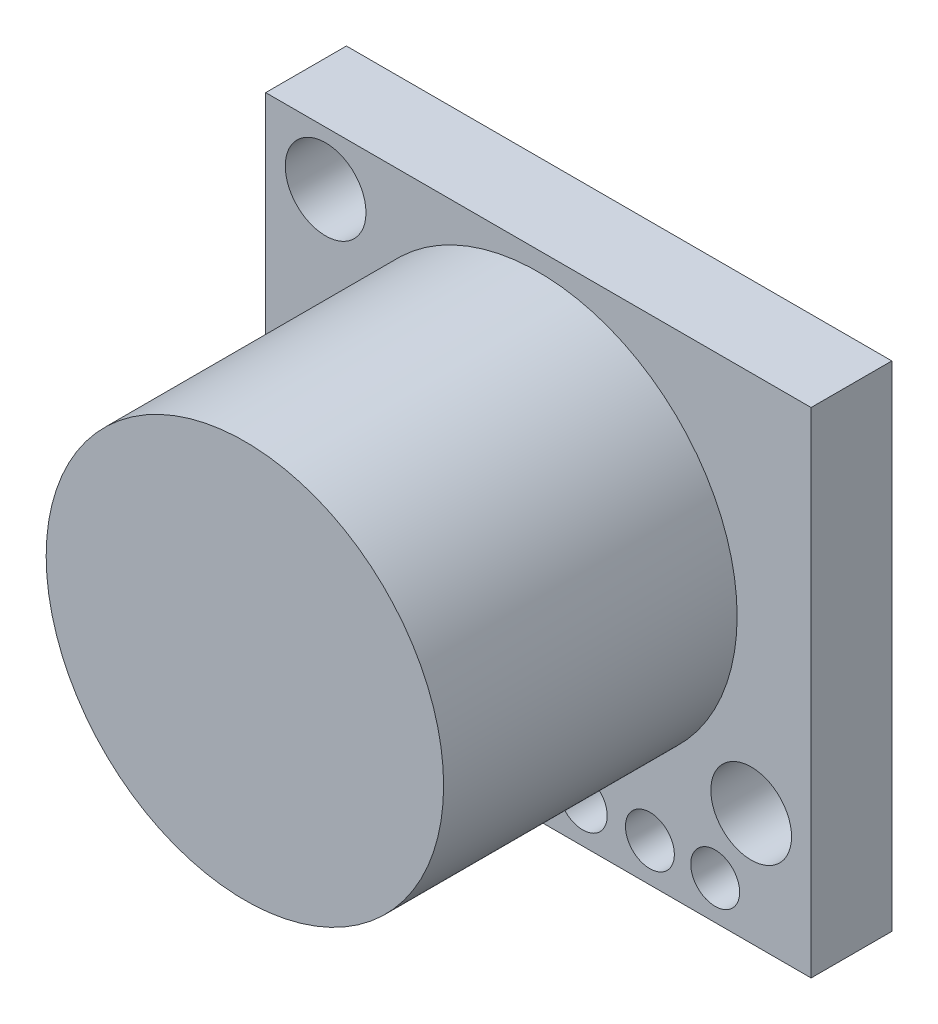
SolidWorks part; units mm, degrees
ref_plane "Front Plane" through (0, 0, 0) normal (0, 0, 1) x (1, 0, 0)
ref_plane "Top Plane" through (0, 0, 0) normal (0, 1, 0) x (1, 0, 0)
ref_plane "Right Plane" through (0, 0, 0) normal (1, 0, 0) x (0, 0, -1)
sketch "Sketch1" plane through (0, 0, 0) normal (0, 0, 1) x (1, 0, 0)
  line L1 (0, 0) -> (22.3, 0)
  line L2 (0, 0) -> (0, 20.2)
  line L3 (0, 20.2) -> (22.3, 20.2)
  line L4 (22.3, 0) -> (22.3, 20.2)
  circle A0 centre (2.45, 18) radius 1.65
  circle A1 centre (19.85, 4.6) radius 1.65
  dimension "D4" = 3.3
  dimension "D5" = 3.3
  dimension "D1" = 22.3
  dimension "D2" = 20.2
  dimension "D3" = 2.2
  dimension "D6" = 2.45
  dimension "D7" = 2.45
  dimension "D8" = 4.6
extrude "Boss-Extrude1" add sketch "Sketch1" along normal blind 3.3
sketch "Sketch2" plane through (0, 0, 3.3) normal (0, 0, 1) x (1, 0, 0)
  line L0 (19.85, 4.6) -> (2.45, 18) construction
  line L1 (4.3535, 1.5743) -> (17.3065, 1.5743) construction
  circle A0 centre (11.15, 11.3) radius 8.125
  circle A3 centre (4.3535, 1.5743) radius 1
  circle A6 centre (7.3803, 1.5743) radius 1
  circle A7 centre (12.9638, 1.5743) radius 1
  circle A8 centre (10.2378, 1.5743) radius 1
  circle A9 centre (15.7086, 1.5743) radius 1
  circle A10 centre (18.3781, 1.5743) radius 1
  dimension "D1" = 16.25
extrude "Boss-Extrude2" add sketch "Sketch2" along normal blind 12 contours A0 region at (11.15, 11.3, 3.3)
extrude "Cut-Extrude1" cut sketch "Sketch2<3>" against normal blind 12 contours A3 | A6 | A8 | A7 | A9 | A10 region at (4.3535, 1.5743, 3.3) region at (7.3803, 1.5743, 3.3) region at (12.9638, 1.5743, 3.3) region at (10.2378, 1.5743, 3.3) region at (15.7086, 1.5743, 3.3) region at (18.3781, 1.5743, 3.3)
sketch "Sketch2<3>" plane through (0, 0, 3.3) normal (0, 0, 1) x (1, 0, 0) same geometry as "Sketch2"
